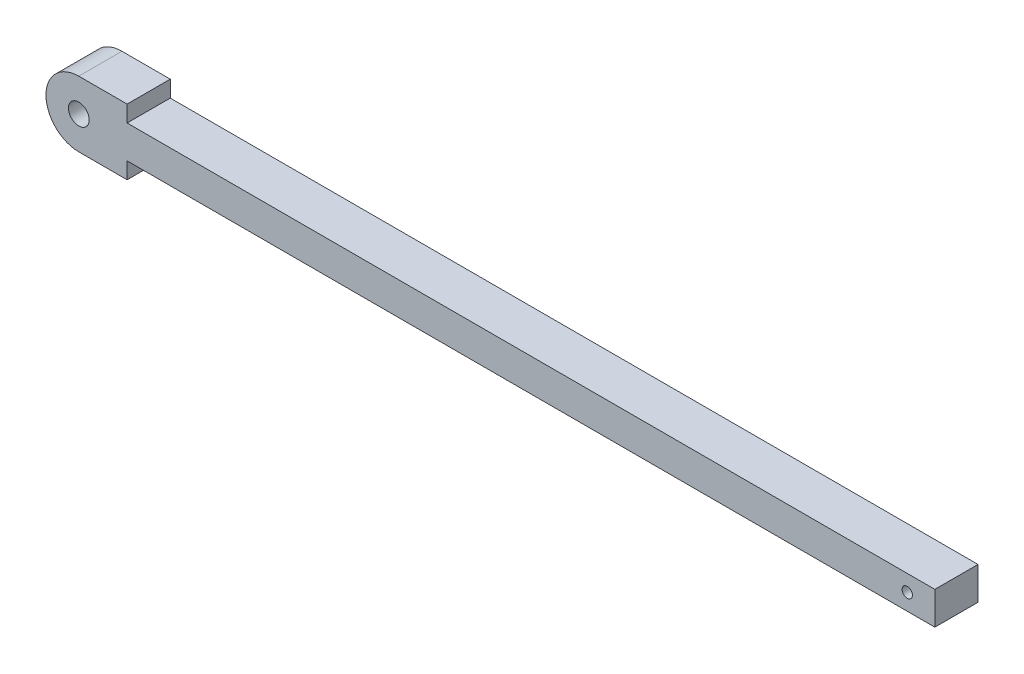
SolidWorks part; units mm, degrees
material "Gray Cast Iron"
ref_plane "Front Plane" through (0, 0, 0) normal (0, 0, 1) x (1, 0, 0)
ref_plane "Top Plane" through (0, 0, 0) normal (0, 1, 0) x (1, 0, 0)
ref_plane "Right Plane" through (0, 0, 0) normal (1, 0, 0) x (0, 0, -1)
sketch "Sketch1" plane through (0, 0, 0) normal (0, 0, 1) x (1, 0, 0)
  line L0 (0, -9.5) -> (14, -9.5)
  line L1 (14, -9.5) -> (14, -4.75)
  line L2 (14, -4.75) -> (248, -4.75)
  line L3 (248, -4.75) -> (248, 4.75)
  line L4 (248, 4.75) -> (14, 4.75)
  line L5 (14, 4.75) -> (14, 9.5)
  line L6 (14, 9.5) -> (0, 9.5)
  arc A0 (0, 9.5) -> (0, -9.5) centre (0, 0) ccw
extrude "Boss-Extrude1" add sketch "Sketch1" along normal blind 12.5
sketch "Sketch2" plane through (0, 0, 0) normal (0, 0, 1) x (1, 0, 0)
  circle A0 centre (0, 0) radius 3
  circle A1 centre (240, 0) radius 1.5
  dimension "D1" = 6
  dimension "D2" = 3
extrude "Cut-Extrude1" cut sketch "Sketch2" against normal mid plane 40
